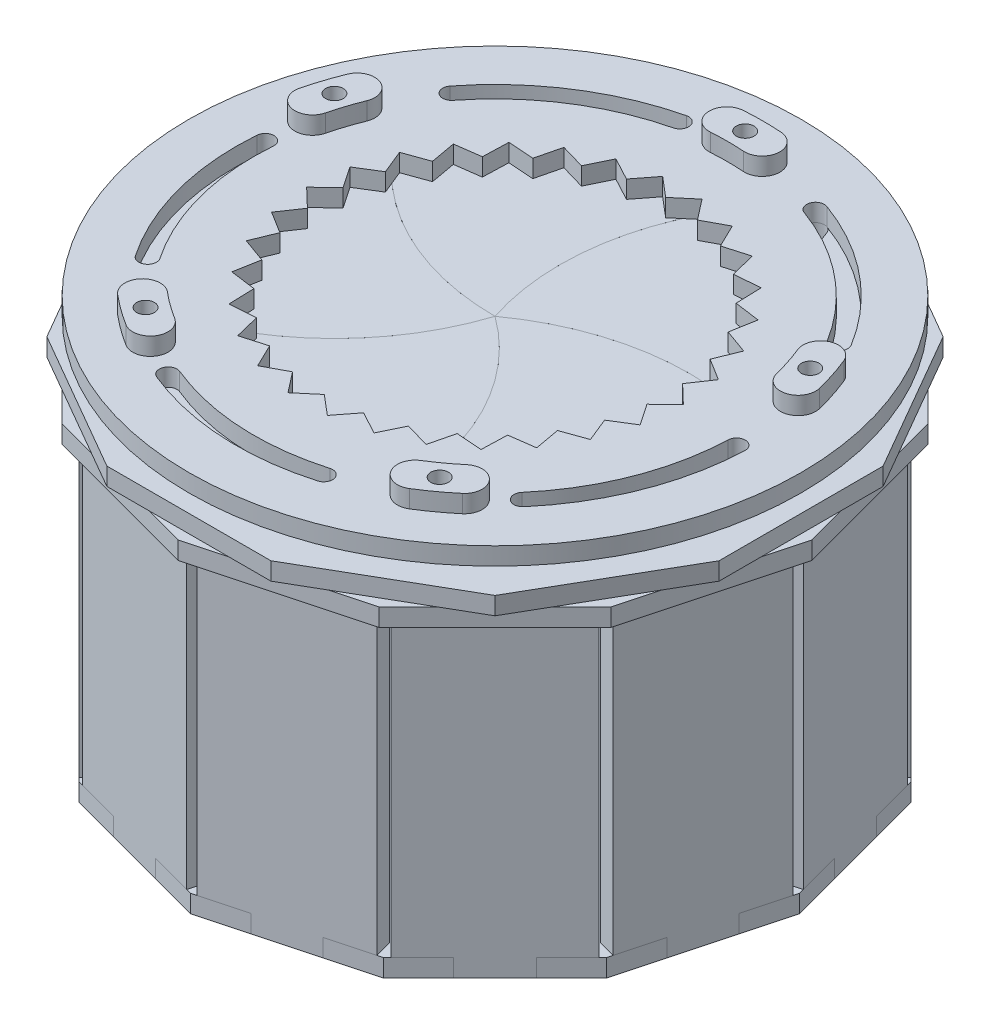
SolidWorks part; units mm, degrees
ref_plane "Front Plane" through (0, 0, 0) normal (0, 0, 1) x (1, 0, 0)
ref_plane "Top Plane" through (0, 0, 0) normal (0, 1, 0) x (1, 0, 0)
ref_plane "Right Plane" through (0, 0, 0) normal (1, 0, 0) x (0, 0, -1)
sketch "Sketch1" plane through (0, 0, 0) normal (0, 1, 0) x (1, 0, 0)
  line L0 (0, 42.5) -> (0, 0) construction
  line L2 (-33.5138, 68.6358) -> (-33.5138, 26.1358) construction
  line L3 (-33.5138, 68.6358) -> (-3.4617, 38.5837) construction
  arc A0 (13.0724, 45.6658) -> (-39.3911, 26.5441) centre (0, 0) ccw
  circle A6 centre (0, 0) radius 42.5 construction
  arc A7 (-39.3911, 26.5441) -> (0, 0) centre (0, 42.5) ccw
  circle A8 centre (0, 42.5) radius 1.5
  arc A9 (39.3911, 26.5441) -> (-39.3911, 26.5441) centre (0, 42.5) ccw construction
  arc A10 (36.8061, 21.25) -> (39.3911, 26.5441) centre (0, 42.5) ccw construction
  arc A11 (0, 0) -> (36.8061, 21.25) centre (0, 42.5) ccw construction
  arc A12 (13.0724, 45.6658) -> (0, 0) centre (40.4199, 13.1332) ccw
  arc A13 (47.4703, 1.6789) -> (0, 0) centre (24.9809, -34.3832) ccw construction
  arc A14 (16.2658, -44.6282) -> (0, 0) centre (-24.9809, -34.3832) ccw construction
  arc A15 (-37.4175, -29.2606) -> (0, 0) centre (-40.4199, 13.1332) ccw construction
  arc A16 (-33.5138, 26.1358) -> (-3.4617, 38.5837) centre (-33.5138, 68.6358) ccw construction
  arc A17 (5.8774, 84.5916) -> (-39.3911, 26.5441) centre (-33.5138, 68.6358) ccw construction
  arc A18 (3.2923, 47.3858) -> (5.8774, 84.5916) centre (-33.5138, 68.6358) ccw construction
  arc A19 (0.9014, 43.6989) -> (3.2923, 47.3858) centre (-33.5138, 68.6358) ccw construction
  arc A20 (0, 42.5) -> (0.9014, 43.6989) centre (-33.5138, 68.6358) ccw construction
  arc A21 (-0.9432, 41.3336) -> (0, 42.5) centre (-33.5138, 68.6358) ccw construction
  arc A22 (-3.4617, 38.5837) -> (-0.9432, 41.3336) centre (-33.5138, 68.6358) ccw construction
  arc A23 (-39.3911, 26.5441) -> (-33.5138, 26.1358) centre (-33.5138, 68.6358) ccw construction
  arc A24 (-3.4617, 38.5837) -> (-33.5138, 26.1358) centre (-33.5138, 68.6358) cw construction
  arc A25 (-33.5138, 24.6358) -> (-2.4011, 37.5231) centre (-33.5138, 68.6358) ccw
  arc A26 (-33.5138, 27.6358) -> (-4.5224, 39.6444) centre (-33.5138, 68.6358) ccw
  arc A27 (-33.5138, 27.6358) -> (-33.5138, 24.6358) centre (-33.5138, 26.1358) ccw
  arc A28 (-2.4011, 37.5231) -> (-4.5224, 39.6444) centre (-3.4617, 38.5837) ccw
  arc A29 (39.3911, 26.5441) -> (13.0724, 45.6658) centre (0, 0) ccw construction
  arc A30 (-39.3911, 26.5441) -> (-37.4175, -29.2606) centre (0, 0) ccw construction
  arc A31 (-37.4175, -29.2606) -> (16.2658, -44.6282) centre (0, 0) ccw construction
  arc A32 (47.4703, 1.6789) -> (39.3911, 26.5441) centre (0, 0) ccw construction
  arc A33 (16.2658, -44.6282) -> (47.4703, 1.6789) centre (0, 0) ccw construction
  point P1 (0, 0)
  point P16 (0, 0)
  point P22 (0, 0)
  point P28 (-17.2497, 29.3709)
  dimension "D1" = 95
  dimension "D3" = 85
  dimension "D5" = 42.5
  dimension "D6" = 5
  dimension "D2" = 3
  dimension "D7" = 1.5
  dimension "D8" = 45
sketch "Sketch3" plane through (0, 0, 0) normal (0, 1, 0) x (1, 0, 0)
  line L0 (8.1113, 49.5904) -> (17.7706, 47.0022)
  line L1 (0, 51.7638) -> (-25.8819, 44.8288) construction
  line L2 (-25.8819, 44.8288) -> (-44.8288, 25.8819) construction
  line L3 (-44.8288, 25.8819) -> (-51.7638, 0) construction
  line L4 (-51.7638, 0) -> (-44.8288, -25.8819) construction
  line L5 (-44.8288, -25.8819) -> (-25.8819, -44.8288) construction
  line L6 (-25.8819, -44.8288) -> (0, -51.7638) construction
  line L7 (0, -51.7638) -> (25.8819, -44.8288) construction
  line L8 (25.8819, -44.8288) -> (44.8288, -25.8819) construction
  line L9 (44.8288, -25.8819) -> (51.7638, 0) construction
  line L10 (51.7638, 0) -> (44.8288, 25.8819) construction
  line L11 (44.8288, 25.8819) -> (25.8819, 44.8288) construction
  line L12 (25.8819, 44.8288) -> (0, 51.7638) construction
  line L13 (8.1113, 49.5904) -> (7.3349, 46.6926)
  line L14 (17.7706, 47.0022) -> (16.9941, 44.1044)
  line L15 (7.3349, 46.6926) -> (16.9941, 44.1044)
  line L16 (12.1645, 45.3985) -> (12.941, 48.2963) construction
  line L17 (26.9172, 46.6219) -> (0, 53.8344)
  line L18 (0, 53.8344) -> (-26.9172, 46.6219)
  line L19 (-26.9172, 46.6219) -> (-46.6219, 26.9172)
  line L20 (-46.6219, 26.9172) -> (-53.8344, 0)
  line L21 (-53.8344, 0) -> (-46.6219, -26.9172)
  line L22 (-46.6219, -26.9172) -> (-26.9172, -46.6219)
  line L23 (-26.9172, -46.6219) -> (0, -53.8344)
  line L24 (0, -53.8344) -> (26.9172, -46.6219)
  line L25 (26.9172, -46.6219) -> (46.6219, -26.9172)
  line L26 (46.6219, -26.9172) -> (53.8344, 0)
  line L27 (53.8344, 0) -> (46.6219, 26.9172)
  line L28 (46.6219, 26.9172) -> (26.9172, 46.6219)
  line L29 (38.8909, 31.8198) -> (36.7696, 29.6985)
  line L30 (31.8198, 38.8909) -> (38.8909, 31.8198)
  line L31 (31.8198, 38.8909) -> (29.6985, 36.7696)
  line L32 (29.6985, 36.7696) -> (36.7696, 29.6985)
  line L33 (33.234, 33.234) -> (35.3553, 35.3553) construction
  line L34 (49.5904, 8.1113) -> (46.6926, 7.3349)
  line L35 (47.0022, 17.7706) -> (49.5904, 8.1113)
  line L36 (47.0022, 17.7706) -> (44.1044, 16.9941)
  line L37 (44.1044, 16.9941) -> (46.6926, 7.3349)
  line L38 (45.3985, 12.1645) -> (48.2963, 12.941) construction
  line L39 (47.0022, -17.7706) -> (44.1044, -16.9941)
  line L40 (49.5904, -8.1113) -> (47.0022, -17.7706)
  line L41 (49.5904, -8.1113) -> (46.6926, -7.3349)
  line L42 (46.6926, -7.3349) -> (44.1044, -16.9941)
  line L43 (45.3985, -12.1645) -> (48.2963, -12.941) construction
  line L44 (31.8198, -38.8909) -> (29.6985, -36.7696)
  line L45 (38.8909, -31.8198) -> (31.8198, -38.8909)
  line L46 (38.8909, -31.8198) -> (36.7696, -29.6985)
  line L47 (36.7696, -29.6985) -> (29.6985, -36.7696)
  line L48 (33.234, -33.234) -> (35.3553, -35.3553) construction
  line L49 (8.1113, -49.5904) -> (7.3349, -46.6926)
  line L50 (17.7706, -47.0022) -> (8.1113, -49.5904)
  line L51 (17.7706, -47.0022) -> (16.9941, -44.1044)
  line L52 (16.9941, -44.1044) -> (7.3349, -46.6926)
  line L53 (12.1645, -45.3985) -> (12.941, -48.2963) construction
  line L54 (-17.7706, -47.0022) -> (-16.9941, -44.1044)
  line L55 (-8.1113, -49.5904) -> (-17.7706, -47.0022)
  line L56 (-8.1113, -49.5904) -> (-7.3349, -46.6926)
  line L57 (-7.3349, -46.6926) -> (-16.9941, -44.1044)
  line L58 (-12.1645, -45.3985) -> (-12.941, -48.2963) construction
  line L59 (-38.8909, -31.8198) -> (-36.7696, -29.6985)
  line L60 (-31.8198, -38.8909) -> (-38.8909, -31.8198)
  line L61 (-31.8198, -38.8909) -> (-29.6985, -36.7696)
  line L62 (-29.6985, -36.7696) -> (-36.7696, -29.6985)
  line L63 (-33.234, -33.234) -> (-35.3553, -35.3553) construction
  line L64 (-49.5904, -8.1113) -> (-46.6926, -7.3349)
  line L65 (-47.0022, -17.7706) -> (-49.5904, -8.1113)
  line L66 (-47.0022, -17.7706) -> (-44.1044, -16.9941)
  line L67 (-44.1044, -16.9941) -> (-46.6926, -7.3349)
  line L68 (-45.3985, -12.1645) -> (-48.2963, -12.941) construction
  line L69 (-47.0022, 17.7706) -> (-44.1044, 16.9941)
  line L70 (-49.5904, 8.1113) -> (-47.0022, 17.7706)
  line L71 (-49.5904, 8.1113) -> (-46.6926, 7.3349)
  line L72 (-46.6926, 7.3349) -> (-44.1044, 16.9941)
  line L73 (-45.3985, 12.1645) -> (-48.2963, 12.941) construction
  line L74 (-31.8198, 38.8909) -> (-29.6985, 36.7696)
  line L75 (-38.8909, 31.8198) -> (-31.8198, 38.8909)
  line L76 (-38.8909, 31.8198) -> (-36.7696, 29.6985)
  line L77 (-36.7696, 29.6985) -> (-29.6985, 36.7696)
  line L78 (-33.234, 33.234) -> (-35.3553, 35.3553) construction
  line L79 (-8.1113, 49.5904) -> (-7.3349, 46.6926)
  line L80 (-17.7706, 47.0022) -> (-8.1113, 49.5904)
  line L81 (-17.7706, 47.0022) -> (-16.9941, 44.1044)
  line L82 (-16.9941, 44.1044) -> (-7.3349, 46.6926)
  line L83 (-12.1645, 45.3985) -> (-12.941, 48.2963) construction
  circle A0 centre (0, 0) radius 50 construction
  circle A2 centre (0, 0) radius 29
  arc A11 (-33.5138, 26.1358) -> (-9.9306, 41.3235) centre (0, 0) cw construction
  arc A20 (-10.281, 42.782) -> (-34.6966, 27.0582) centre (0, 0) ccw
  circle A22 centre (0, 0) radius 42.5 construction
  circle A23 centre (0, 0) radius 42.5 construction
  arc A24 (-9.5801, 39.8651) -> (-32.3309, 25.2133) centre (0, 0) ccw
  arc A25 (-9.5801, 39.8651) -> (-10.281, 42.782) centre (-9.9306, 41.3235) ccw
  arc A26 (-34.6966, 27.0582) -> (-32.3309, 25.2133) centre (-33.5138, 26.1358) ccw
  circle A27 centre (0, 42.5) radius 10 construction
  circle A28 centre (0, 42.5) radius 1.5 construction
  circle A29 centre (0, 42.5) radius 1.5
  circle A30 centre (40.4199, 13.1332) radius 1.5
  arc A31 (14.5003, 39.9499) -> (36.2323, 22.2142) centre (0, 0) cw construction
  arc A32 (37.5111, 22.9982) -> (15.012, 41.3599) centre (0, 0) ccw
  arc A33 (34.9535, 21.4302) -> (13.9885, 38.5399) centre (0, 0) ccw
  arc A34 (34.9535, 21.4302) -> (37.5111, 22.9982) centre (36.2323, 22.2142) ccw
  arc A35 (15.012, 41.3599) -> (13.9885, 38.5399) centre (14.5003, 39.9499) ccw
  circle A36 centre (24.9809, -34.3832) radius 1.5
  arc A37 (42.4754, -1.4454) -> (32.3233, -27.5944) centre (0, 0) cw construction
  arc A38 (33.4642, -28.5683) -> (43.9745, -1.4964) centre (0, 0) ccw
  arc A39 (31.1825, -26.6205) -> (40.9763, -1.3944) centre (0, 0) ccw
  arc A40 (31.1825, -26.6205) -> (33.4642, -28.5683) centre (32.3233, -27.5944) ccw
  arc A41 (43.9745, -1.4964) -> (40.9763, -1.3944) centre (42.4754, -1.4454) ccw
  circle A42 centre (-24.9809, -34.3832) radius 1.5
  arc A43 (11.751, -40.8432) -> (-16.2554, -39.2685) centre (0, 0) cw construction
  arc A44 (-16.8291, -40.6544) -> (12.1657, -42.2847) centre (0, 0) ccw
  arc A45 (-15.6817, -37.8825) -> (11.3362, -39.4016) centre (0, 0) ccw
  arc A46 (-15.6817, -37.8825) -> (-16.8291, -40.6544) centre (-16.2554, -39.2685) ccw
  arc A47 (12.1657, -42.2847) -> (11.3362, -39.4016) centre (11.751, -40.8432) ccw
  circle A48 centre (-40.4199, 13.1332) radius 1.5
  arc A49 (-35.2129, -23.7971) -> (-42.3697, 3.3252) centre (0, 0) cw construction
  arc A50 (-43.8651, 3.4425) -> (-36.4557, -24.637) centre (0, 0) ccw
  arc A51 (-40.8743, 3.2078) -> (-33.9701, -22.9572) centre (0, 0) ccw
  arc A52 (-40.8743, 3.2078) -> (-43.8651, 3.4425) centre (-42.3697, 3.3252) ccw
  arc A53 (-36.4557, -24.637) -> (-33.9701, -22.9572) centre (-35.2129, -23.7971) ccw
  circle A54 centre (0, 0) radius 52 construction
  point P1 (-23.0113, 35.7314)
  point P102 (0, 0)
  point P106 (-9.9306, 41.3235)
  point P121 (26.8717, 32.9266)
  point P132 (39.6189, -15.3816)
  point P141 (-2.3859, -42.433)
  point P150 (-41.0934, -10.8434)
  point P159 (0, 0)
  dimension "D1" = 100
  dimension "D6" = 58
  dimension "D7" = 1.5
  dimension "D8" = 20
  dimension "D2" = 3
  dimension "D3" = 10
  dimension "D4" = 2
  dimension "D5" = 12
  dimension "D9" = 5
sketch "Sketch4" plane through (0, 0, 0) normal (0, 1, 0) x (1, 0, 0)
  arc A0 (6.0367, 38.1141) -> (5.8444, 47.1391) centre (0, 42.5) ccw
  circle A1 centre (0, 42.5) radius 1.5
  circle A2 centre (0, 42.5) radius 1.5
  arc A3 (-5.8444, 47.1391) -> (-6.0765, 38.1694) centre (0, 42.5) ccw construction
  arc A4 (5.8444, 47.1391) -> (-5.8444, 47.1391) centre (0, 42.5) ccw construction
  arc A5 (13.0724, 45.6658) -> (-39.3911, 26.5441) centre (0, 0) ccw
  arc A6 (-39.3911, 26.5441) -> (0, 0) centre (0, 42.5) ccw
  arc A7 (13.0724, 45.6658) -> (0, 0) centre (40.4199, 13.1332) ccw
  arc A8 (5.8444, 47.1391) -> (-39.3911, 26.5441) centre (0, 0) ccw
  arc A9 (-39.3911, 26.5441) -> (0, 0) centre (0, 42.5) ccw
  arc A10 (6.0367, 38.1141) -> (0, 0) centre (40.4199, 13.1332) ccw
  arc A11 (-6.0765, 38.1694) -> (-3.8701, 36.1203) centre (0, 42.5) ccw construction
  arc A12 (-2.4011, 37.5231) -> (-4.5224, 39.6444) centre (-3.4617, 38.5837) ccw
  arc A13 (-33.5138, 24.6358) -> (-2.4011, 37.5231) centre (-33.5138, 68.6358) ccw
  arc A14 (-33.5138, 27.6358) -> (-33.5138, 24.6358) centre (-33.5138, 26.1358) ccw
  arc A15 (-33.5138, 27.6358) -> (-4.5224, 39.6444) centre (-33.5138, 68.6358) ccw
  arc A16 (-2.4011, 37.5231) -> (-4.5224, 39.6444) centre (-3.4617, 38.5837) ccw
  arc A17 (-33.5138, 24.6358) -> (-2.4011, 37.5231) centre (-33.5138, 68.6358) ccw
  arc A18 (-33.5138, 27.6358) -> (-33.5138, 24.6358) centre (-33.5138, 26.1358) ccw
  arc A19 (-33.5138, 27.6358) -> (-4.5224, 39.6444) centre (-33.5138, 68.6358) ccw
  arc A20 (-3.8701, 36.1203) -> (6.0367, 38.1141) centre (0, 42.5) ccw construction
  arc A21 (13.0724, 45.6658) -> (6.0367, 38.1141) centre (40.4199, 13.1332) ccw construction
  arc A22 (13.0724, 45.6658) -> (5.8444, 47.1391) centre (0, 0) ccw construction
  arc A23 (5.738, 46.9507) -> (-39.1657, 26.5206) centre (0, 0) ccw construction
  arc A24 (-39.1657, 26.5206) -> (-0.2746, 0.2009) centre (0, 42.5) ccw construction
  arc A25 (5.8749, 38.2317) -> (-0.2746, 0.2009) centre (40.4199, 13.1332) ccw construction
  arc A26 (5.8749, 38.2317) -> (5.738, 46.9507) centre (0, 42.5) ccw construction
  dimension "D1" = 0
  dimension "D2" = 0
  dimension "D3" = 0
  dimension "D4" = 0.2
extrude "Boss-Extrude1" add sketch "Sketch4" against normal blind 3
sketch "Sketch5" plane through (0, 0, 0) normal (0, 1, 0) x (1, 0, 0)
  line L0 (0, 0) -> (0, 32) construction
  line L1 (0, 0) -> (3.3449, 31.8247) construction
  line L2 (0, 0) -> (-3.3449, 31.8247) construction
  line L3 (-3.3449, 31.8247) -> (0, 29)
  line L4 (0, 29) -> (3.3449, 31.8247)
  line L6 (3.3449, 31.8247) -> (6.0294, 28.3663)
  line L7 (6.0294, 28.3663) -> (9.8885, 30.4338)
  line L8 (9.8885, 30.4338) -> (11.7954, 26.4928)
  line L9 (11.7954, 26.4928) -> (16, 27.7128)
  line L10 (16, 27.7128) -> (17.0458, 23.4615)
  line L11 (17.0458, 23.4615) -> (21.4122, 23.7806)
  line L12 (21.4122, 23.7806) -> (21.5512, 19.4048)
  line L13 (21.5512, 19.4048) -> (25.8885, 18.8091)
  line L14 (25.8885, 18.8091) -> (25.1147, 14.5)
  line L15 (25.1147, 14.5) -> (29.2335, 13.0156)
  line L16 (29.2335, 13.0156) -> (27.5806, 8.9615)
  line L17 (27.5806, 8.9615) -> (31.3007, 6.6532)
  line L18 (31.3007, 6.6532) -> (28.8411, 3.0313)
  line L19 (28.8411, 3.0313) -> (32, 0)
  line L20 (32, 0) -> (28.8411, -3.0313)
  line L21 (28.8411, -3.0313) -> (31.3007, -6.6532)
  line L22 (31.3007, -6.6532) -> (27.5806, -8.9615)
  line L23 (27.5806, -8.9615) -> (29.2335, -13.0156)
  line L24 (29.2335, -13.0156) -> (25.1147, -14.5)
  line L25 (25.1147, -14.5) -> (25.8885, -18.8091)
  line L26 (25.8885, -18.8091) -> (21.5512, -19.4048)
  line L27 (21.5512, -19.4048) -> (21.4122, -23.7806)
  line L28 (21.4122, -23.7806) -> (17.0458, -23.4615)
  line L29 (17.0458, -23.4615) -> (16, -27.7128)
  line L30 (16, -27.7128) -> (11.7954, -26.4928)
  line L31 (11.7954, -26.4928) -> (9.8885, -30.4338)
  line L32 (9.8885, -30.4338) -> (6.0294, -28.3663)
  line L33 (6.0294, -28.3663) -> (3.3449, -31.8247)
  line L34 (3.3449, -31.8247) -> (0, -29)
  line L35 (0, -29) -> (-3.3449, -31.8247)
  line L36 (-3.3449, -31.8247) -> (-6.0294, -28.3663)
  line L37 (-6.0294, -28.3663) -> (-9.8885, -30.4338)
  line L38 (-9.8885, -30.4338) -> (-11.7954, -26.4928)
  line L39 (-11.7954, -26.4928) -> (-16, -27.7128)
  line L40 (-16, -27.7128) -> (-17.0458, -23.4615)
  line L41 (-17.0458, -23.4615) -> (-21.4122, -23.7806)
  line L42 (-21.4122, -23.7806) -> (-21.5512, -19.4048)
  line L43 (-21.5512, -19.4048) -> (-25.8885, -18.8091)
  line L44 (-25.8885, -18.8091) -> (-25.1147, -14.5)
  line L45 (-25.1147, -14.5) -> (-29.2335, -13.0156)
  line L46 (-29.2335, -13.0156) -> (-27.5806, -8.9615)
  line L47 (-27.5806, -8.9615) -> (-31.3007, -6.6532)
  line L48 (-31.3007, -6.6532) -> (-28.8411, -3.0313)
  line L49 (-28.8411, -3.0313) -> (-32, 0)
  line L50 (-32, 0) -> (-28.8411, 3.0313)
  line L51 (-28.8411, 3.0313) -> (-31.3007, 6.6532)
  line L52 (-31.3007, 6.6532) -> (-27.5806, 8.9615)
  line L53 (-27.5806, 8.9615) -> (-29.2335, 13.0156)
  line L54 (-29.2335, 13.0156) -> (-25.1147, 14.5)
  line L55 (-25.1147, 14.5) -> (-25.8885, 18.8091)
  line L56 (-25.8885, 18.8091) -> (-21.5512, 19.4048)
  line L57 (-21.5512, 19.4048) -> (-21.4122, 23.7806)
  line L58 (-21.4122, 23.7806) -> (-17.0458, 23.4615)
  line L59 (-17.0458, 23.4615) -> (-16, 27.7128)
  line L60 (-16, 27.7128) -> (-11.7954, 26.4928)
  line L61 (-11.7954, 26.4928) -> (-9.8885, 30.4338)
  line L62 (-9.8885, 30.4338) -> (-6.0294, 28.3663)
  line L63 (-6.0294, 28.3663) -> (-3.3449, 31.8247)
  circle A2 centre (0, 0) radius 32 construction
  circle A3 centre (0, 0) radius 52 construction
  circle A4 centre (0, 0) radius 52
  circle A6 centre (24.9809, -34.3832) radius 1.35
  circle A7 centre (0, 0) radius 29
  circle A8 centre (0, 0) radius 29 construction
  circle A9 centre (0, 42.5) radius 1.5
  circle A10 centre (0, 42.5) radius 1.5 construction
  circle A11 centre (24.9809, -34.3832) radius 1.5
  circle A12 centre (24.9809, -34.3832) radius 1.5 construction
  circle A13 centre (40.4199, 13.1332) radius 1.5
  arc A14 (-9.5801, 39.8651) -> (-32.3309, 25.2133) centre (0, 0) ccw
  arc A15 (-9.5801, 39.8651) -> (-10.281, 42.782) centre (-9.9306, 41.3235) ccw
  arc A16 (-10.281, 42.782) -> (-34.6966, 27.0582) centre (0, 0) ccw
  arc A17 (-34.6966, 27.0582) -> (-32.3309, 25.2133) centre (-33.5138, 26.1358) ccw
  arc A18 (-9.5801, 39.8651) -> (-32.3309, 25.2133) centre (0, 0) ccw
  arc A19 (-9.5801, 39.8651) -> (-10.281, 42.782) centre (-9.9306, 41.3235) ccw
  arc A20 (-10.281, 42.782) -> (-34.6966, 27.0582) centre (0, 0) ccw
  arc A21 (-34.6966, 27.0582) -> (-32.3309, 25.2133) centre (-33.5138, 26.1358) ccw
  arc A22 (33.4642, -28.5683) -> (43.9745, -1.4964) centre (0, 0) ccw
  arc A23 (43.9745, -1.4964) -> (40.9763, -1.3944) centre (42.4754, -1.4454) ccw
  arc A24 (31.1825, -26.6205) -> (40.9763, -1.3944) centre (0, 0) ccw
  arc A25 (31.1825, -26.6205) -> (33.4642, -28.5683) centre (32.3233, -27.5944) ccw
  arc A26 (33.4642, -28.5683) -> (43.9745, -1.4964) centre (0, 0) ccw
  arc A27 (43.9745, -1.4964) -> (40.9763, -1.3944) centre (42.4754, -1.4454) ccw
  arc A28 (31.1825, -26.6205) -> (40.9763, -1.3944) centre (0, 0) ccw
  arc A29 (31.1825, -26.6205) -> (33.4642, -28.5683) centre (32.3233, -27.5944) ccw
  circle A30 centre (40.4199, 13.1332) radius 1.5 construction
  circle A31 centre (-40.4199, 13.1332) radius 1.5
  arc A32 (15.012, 41.3599) -> (13.9885, 38.5399) centre (14.5003, 39.9499) ccw
  arc A33 (37.5111, 22.9982) -> (15.012, 41.3599) centre (0, 0) ccw
  arc A34 (34.9535, 21.4302) -> (37.5111, 22.9982) centre (36.2323, 22.2142) ccw
  arc A35 (34.9535, 21.4302) -> (13.9885, 38.5399) centre (0, 0) ccw
  arc A36 (15.012, 41.3599) -> (13.9885, 38.5399) centre (14.5003, 39.9499) ccw
  arc A37 (37.5111, 22.9982) -> (15.012, 41.3599) centre (0, 0) ccw
  arc A38 (34.9535, 21.4302) -> (37.5111, 22.9982) centre (36.2323, 22.2142) ccw
  arc A39 (34.9535, 21.4302) -> (13.9885, 38.5399) centre (0, 0) ccw
  circle A40 centre (-40.4199, 13.1332) radius 1.5 construction
  circle A41 centre (-24.9809, -34.3832) radius 1.5
  arc A42 (-43.8651, 3.4425) -> (-36.4557, -24.637) centre (0, 0) ccw
  arc A43 (-36.4557, -24.637) -> (-33.9701, -22.9572) centre (-35.2129, -23.7971) ccw
  arc A44 (-40.8743, 3.2078) -> (-33.9701, -22.9572) centre (0, 0) ccw
  arc A45 (-40.8743, 3.2078) -> (-43.8651, 3.4425) centre (-42.3697, 3.3252) ccw
  arc A46 (-43.8651, 3.4425) -> (-36.4557, -24.637) centre (0, 0) ccw
  arc A47 (-36.4557, -24.637) -> (-33.9701, -22.9572) centre (-35.2129, -23.7971) ccw
  arc A48 (-40.8743, 3.2078) -> (-33.9701, -22.9572) centre (0, 0) ccw
  arc A49 (-40.8743, 3.2078) -> (-43.8651, 3.4425) centre (-42.3697, 3.3252) ccw
  circle A50 centre (-24.9809, -34.3832) radius 1.5 construction
  circle A51 centre (40.4199, 13.1332) radius 1.35
  arc A52 (-15.6817, -37.8825) -> (11.3362, -39.4016) centre (0, 0) ccw
  arc A53 (12.1657, -42.2847) -> (11.3362, -39.4016) centre (11.751, -40.8432) ccw
  arc A54 (-16.8291, -40.6544) -> (12.1657, -42.2847) centre (0, 0) ccw
  arc A55 (-15.6817, -37.8825) -> (-16.8291, -40.6544) centre (-16.2554, -39.2685) ccw
  arc A56 (-15.6817, -37.8825) -> (11.3362, -39.4016) centre (0, 0) ccw
  arc A57 (12.1657, -42.2847) -> (11.3362, -39.4016) centre (11.751, -40.8432) ccw
  arc A58 (-16.8291, -40.6544) -> (12.1657, -42.2847) centre (0, 0) ccw
  arc A59 (-15.6817, -37.8825) -> (-16.8291, -40.6544) centre (-16.2554, -39.2685) ccw
  circle A60 centre (-24.9809, -34.3832) radius 1.35
  circle A61 centre (-40.4199, 13.1332) radius 1.35
  circle A62 centre (0, 42.5) radius 1.35
  point P166 (0, 0)
  dimension "D4" = 3
  dimension "D3" = 2.7
  dimension "D5" = 6
  dimension "D6" = 6
  dimension "D2" = 0
  dimension "D7" = 30
  dimension "D15" = 0
  dimension "D16" = 0
  dimension "D17" = 0
  dimension "D18" = 0
  dimension "D19" = 0
  dimension "D20" = 0
  dimension "D21" = 0
  dimension "D22" = 0
  dimension "D23" = 0
  dimension "D24" = 0
extrude "Boss-Extrude2" add sketch "Sketch5" along normal blind 3 separate body
sketch "Sketch8" plane through (0, 0, 0) normal (0, 1, 0) x (1, 0, 0)
  line L0 (26.9172, 46.6219) -> (0, 53.8344) construction
  line L1 (13.9334, 52) -> (-13.9334, 52)
  line L2 (-13.9334, 52) -> (-38.0666, 38.0666)
  line L3 (-38.0666, 38.0666) -> (-52, 13.9334)
  line L4 (-52, 13.9334) -> (-52, -13.9334)
  line L5 (-52, -13.9334) -> (-38.0666, -38.0666)
  line L6 (-38.0666, -38.0666) -> (-13.9334, -52)
  line L7 (-13.9334, -52) -> (13.9334, -52)
  line L8 (13.9334, -52) -> (38.0666, -38.0666)
  line L9 (38.0666, -38.0666) -> (52, -13.9334)
  line L10 (52, -13.9334) -> (52, 13.9334)
  line L11 (52, 13.9334) -> (38.0666, 38.0666)
  line L12 (38.0666, 38.0666) -> (13.9334, 52)
  circle A0 centre (14.5003, 39.9499) radius 1.35
  circle A1 centre (42.4754, -1.4454) radius 1.35
  circle A2 centre (11.751, -40.8432) radius 1.35
  circle A3 centre (-35.2129, -23.7971) radius 1.35
  circle A4 centre (-33.5138, 26.1358) radius 1.35
  circle A5 centre (0, 0) radius 52 construction
  circle A8 centre (0, 0) radius 37
  circle A9 centre (0, 0) radius 37
  point P3 (0, 52)
  point P14 (0, 0)
  dimension "D1" = 2.7
  dimension "D3" = 8
  dimension "D2" = 5
extrude "Boss-Extrude5" add sketch "Sketch8" against normal blind 3 from surface separate body starting at face at (-17.9786, -3, -31.1305)
sketch "Sketch6" plane through (0, 0, 0) normal (0, 1, 0) x (1, 0, 0)
  line L4 (17.7706, 47.0022) -> (8.1113, 49.5904)
  line L5 (16.9941, 44.1044) -> (17.7706, 47.0022)
  line L6 (7.3349, 46.6926) -> (16.9941, 44.1044)
  line L7 (8.1113, 49.5904) -> (7.3349, 46.6926)
  line L8 (17.7706, 47.0022) -> (8.1113, 49.5904)
  line L9 (16.9941, 44.1044) -> (17.7706, 47.0022)
  line L10 (7.3349, 46.6926) -> (16.9941, 44.1044)
  line L11 (8.1113, 49.5904) -> (7.3349, 46.6926)
  line L12 (46.6926, 7.3349) -> (49.5904, 8.1113)
  line L13 (44.1044, 16.9941) -> (46.6926, 7.3349)
  line L14 (47.0022, 17.7706) -> (44.1044, 16.9941)
  line L15 (49.5904, 8.1113) -> (47.0022, 17.7706)
  line L16 (46.6926, 7.3349) -> (49.5904, 8.1113)
  line L17 (44.1044, 16.9941) -> (46.6926, 7.3349)
  line L18 (47.0022, 17.7706) -> (44.1044, 16.9941)
  line L19 (49.5904, 8.1113) -> (47.0022, 17.7706)
  line L20 (36.7696, 29.6985) -> (38.8909, 31.8198)
  line L21 (29.6985, 36.7696) -> (36.7696, 29.6985)
  line L22 (31.8198, 38.8909) -> (29.6985, 36.7696)
  line L23 (38.8909, 31.8198) -> (31.8198, 38.8909)
  line L24 (36.7696, 29.6985) -> (38.8909, 31.8198)
  line L25 (29.6985, 36.7696) -> (36.7696, 29.6985)
  line L26 (31.8198, 38.8909) -> (29.6985, 36.7696)
  line L27 (38.8909, 31.8198) -> (31.8198, 38.8909)
  line L28 (29.6985, -36.7696) -> (31.8198, -38.8909)
  line L29 (36.7696, -29.6985) -> (29.6985, -36.7696)
  line L30 (38.8909, -31.8198) -> (36.7696, -29.6985)
  line L31 (31.8198, -38.8909) -> (38.8909, -31.8198)
  line L32 (29.6985, -36.7696) -> (31.8198, -38.8909)
  line L33 (36.7696, -29.6985) -> (29.6985, -36.7696)
  line L34 (38.8909, -31.8198) -> (36.7696, -29.6985)
  line L35 (31.8198, -38.8909) -> (38.8909, -31.8198)
  line L36 (46.6219, -26.9172) -> (53.8344, 0)
  line L37 (53.8344, 0) -> (46.6219, 26.9172)
  line L38 (46.6219, 26.9172) -> (26.9172, 46.6219)
  line L39 (26.9172, 46.6219) -> (0, 53.8344)
  line L40 (0, 53.8344) -> (-26.9172, 46.6219)
  line L41 (-26.9172, 46.6219) -> (-46.6219, 26.9172)
  line L42 (-46.6219, 26.9172) -> (-53.8344, 0)
  line L43 (-53.8344, 0) -> (-46.6219, -26.9172)
  line L44 (-46.6219, -26.9172) -> (-26.9172, -46.6219)
  line L45 (-26.9172, -46.6219) -> (0, -53.8344)
  line L46 (0, -53.8344) -> (26.9172, -46.6219)
  line L47 (26.9172, -46.6219) -> (46.6219, -26.9172)
  line L48 (46.6219, -26.9172) -> (53.8344, 0)
  line L49 (53.8344, 0) -> (46.6219, 26.9172)
  line L50 (46.6219, 26.9172) -> (26.9172, 46.6219)
  line L51 (26.9172, 46.6219) -> (0, 53.8344)
  line L52 (0, 53.8344) -> (-26.9172, 46.6219)
  line L53 (-26.9172, 46.6219) -> (-46.6219, 26.9172)
  line L54 (-46.6219, 26.9172) -> (-53.8344, 0)
  line L55 (-53.8344, 0) -> (-46.6219, -26.9172)
  line L56 (-46.6219, -26.9172) -> (-26.9172, -46.6219)
  line L57 (-26.9172, -46.6219) -> (0, -53.8344)
  line L58 (0, -53.8344) -> (26.9172, -46.6219)
  line L59 (26.9172, -46.6219) -> (46.6219, -26.9172)
  line L60 (44.1044, -16.9941) -> (47.0022, -17.7706)
  line L61 (46.6926, -7.3349) -> (44.1044, -16.9941)
  line L62 (49.5904, -8.1113) -> (46.6926, -7.3349)
  line L63 (47.0022, -17.7706) -> (49.5904, -8.1113)
  line L64 (44.1044, -16.9941) -> (47.0022, -17.7706)
  line L65 (46.6926, -7.3349) -> (44.1044, -16.9941)
  line L66 (49.5904, -8.1113) -> (46.6926, -7.3349)
  line L67 (47.0022, -17.7706) -> (49.5904, -8.1113)
  line L68 (-36.7696, -29.6985) -> (-38.8909, -31.8198)
  line L69 (-29.6985, -36.7696) -> (-36.7696, -29.6985)
  line L70 (-31.8198, -38.8909) -> (-29.6985, -36.7696)
  line L71 (-38.8909, -31.8198) -> (-31.8198, -38.8909)
  line L72 (-36.7696, -29.6985) -> (-38.8909, -31.8198)
  line L73 (-29.6985, -36.7696) -> (-36.7696, -29.6985)
  line L74 (-31.8198, -38.8909) -> (-29.6985, -36.7696)
  line L75 (-38.8909, -31.8198) -> (-31.8198, -38.8909)
  line L76 (-16.9941, -44.1044) -> (-17.7706, -47.0022)
  line L77 (-7.3349, -46.6926) -> (-16.9941, -44.1044)
  line L78 (-8.1113, -49.5904) -> (-7.3349, -46.6926)
  line L79 (-17.7706, -47.0022) -> (-8.1113, -49.5904)
  line L80 (-16.9941, -44.1044) -> (-17.7706, -47.0022)
  line L81 (-7.3349, -46.6926) -> (-16.9941, -44.1044)
  line L82 (-8.1113, -49.5904) -> (-7.3349, -46.6926)
  line L83 (-17.7706, -47.0022) -> (-8.1113, -49.5904)
  line L84 (16.9941, -44.1044) -> (7.3349, -46.6926)
  line L85 (7.3349, -46.6926) -> (8.1113, -49.5904)
  line L86 (8.1113, -49.5904) -> (17.7706, -47.0022)
  line L87 (17.7706, -47.0022) -> (16.9941, -44.1044)
  line L88 (16.9941, -44.1044) -> (7.3349, -46.6926)
  line L89 (7.3349, -46.6926) -> (8.1113, -49.5904)
  line L90 (8.1113, -49.5904) -> (17.7706, -47.0022)
  line L91 (17.7706, -47.0022) -> (16.9941, -44.1044)
  line L92 (-29.6985, 36.7696) -> (-31.8198, 38.8909)
  line L93 (-36.7696, 29.6985) -> (-29.6985, 36.7696)
  line L94 (-38.8909, 31.8198) -> (-36.7696, 29.6985)
  line L95 (-31.8198, 38.8909) -> (-38.8909, 31.8198)
  line L96 (-29.6985, 36.7696) -> (-31.8198, 38.8909)
  line L97 (-36.7696, 29.6985) -> (-29.6985, 36.7696)
  line L98 (-38.8909, 31.8198) -> (-36.7696, 29.6985)
  line L99 (-31.8198, 38.8909) -> (-38.8909, 31.8198)
  line L100 (-44.1044, 16.9941) -> (-47.0022, 17.7706)
  line L101 (-46.6926, 7.3349) -> (-44.1044, 16.9941)
  line L102 (-49.5904, 8.1113) -> (-46.6926, 7.3349)
  line L103 (-47.0022, 17.7706) -> (-49.5904, 8.1113)
  line L104 (-44.1044, 16.9941) -> (-47.0022, 17.7706)
  line L105 (-46.6926, 7.3349) -> (-44.1044, 16.9941)
  line L106 (-49.5904, 8.1113) -> (-46.6926, 7.3349)
  line L107 (-47.0022, 17.7706) -> (-49.5904, 8.1113)
  line L108 (-46.6926, -7.3349) -> (-49.5904, -8.1113)
  line L109 (-49.5904, -8.1113) -> (-47.0022, -17.7706)
  line L110 (-47.0022, -17.7706) -> (-44.1044, -16.9941)
  line L111 (-44.1044, -16.9941) -> (-46.6926, -7.3349)
  line L112 (-46.6926, -7.3349) -> (-49.5904, -8.1113)
  line L113 (-49.5904, -8.1113) -> (-47.0022, -17.7706)
  line L114 (-47.0022, -17.7706) -> (-44.1044, -16.9941)
  line L115 (-44.1044, -16.9941) -> (-46.6926, -7.3349)
  line L116 (-7.3349, 46.6926) -> (-8.1113, 49.5904)
  line L117 (-16.9941, 44.1044) -> (-7.3349, 46.6926)
  line L118 (-17.7706, 47.0022) -> (-16.9941, 44.1044)
  line L119 (-8.1113, 49.5904) -> (-17.7706, 47.0022)
  line L120 (-7.3349, 46.6926) -> (-8.1113, 49.5904)
  line L121 (-16.9941, 44.1044) -> (-7.3349, 46.6926)
  line L122 (-17.7706, 47.0022) -> (-16.9941, 44.1044)
  line L123 (-8.1113, 49.5904) -> (-17.7706, 47.0022)
  circle A0 centre (0, 0) radius 37
  circle A1 centre (0, 0) radius 29
  circle A2 centre (0, 0) radius 29 construction
  circle A5 centre (-33.5138, 26.1358) radius 1.35
  circle A45 centre (14.5003, 39.9499) radius 1.35
  circle A54 centre (42.4754, -1.4454) radius 1.35
  circle A55 centre (11.751, -40.8432) radius 1.35
  circle A56 centre (-35.2129, -23.7971) radius 1.35
  point P68 (0, 0)
  point P70 (44.4754, 0.5535)
  point P71 (0, 0)
  point P87 (0, 0)
  dimension "D16" = 2.7
  dimension "D1" = 0
  dimension "D2" = 0
  dimension "D3" = 0
  dimension "D4" = 0
  dimension "D5" = 0
  dimension "D6" = 0
  dimension "D7" = 0
  dimension "D8" = 0
  dimension "D9" = 0
  dimension "D10" = 0
  dimension "D11" = 0
  dimension "D12" = 0
  dimension "D13" = 0
  dimension "D14" = 0
  dimension "D15" = 8
  dimension "D18" = 5
extrude "Boss-Extrude6" add sketch "Sketch6" against normal blind 3 from surface separate body starting at face at (0, -6, 37)
sketch "Sketch7" plane through (0, 0, 0) normal (0, 1, 0) x (1, 0, 0)
  circle A16 centre (0, 42.5) radius 1.5 construction
  arc A20 (-3, 42.394) -> (3, 42.394) centre (0, 0) cw construction
  arc A22 (3.2118, 45.3865) -> (-3.2118, 45.3865) centre (0, 0) ccw
  arc A23 (2.7882, 39.4015) -> (-2.7882, 39.4015) centre (0, 0) ccw
  arc A24 (2.7882, 39.4015) -> (3.2118, 45.3865) centre (3, 42.394) ccw
  arc A25 (-3.2118, 45.3865) -> (-2.7882, 39.4015) centre (-3, 42.394) ccw
  circle A26 centre (0, 42.5) radius 1.5
  point P5 (0, 42.5)
  dimension "D1" = 3
  dimension "D2" = 6
  dimension "D3" = 3
extrude "Boss-Extrude4" add sketch "Sketch7" along normal blind 3 from surface separate body starting at face at (-40.4199, 3, -11.7832)
ref_plane "Plane2" through (-12.1645, 0, -45.3985) normal (-0.2588, 0, -0.9659) x (-0.9659, 0, 0.2588)
sketch "Sketch9" plane through (-12.1645, 0, -45.3985) normal (-0.2588, 0, -0.9659) x (-0.9659, 0, 0.2588)
  line L0 (-13.9334, -9) -> (13.9334, -9) construction
  line L1 (12.5, -59) -> (-12.5, -59)
  line L2 (12.5, -59) -> (12.5, -9)
  line L3 (12.5, -9) -> (-12.5, -9)
  line L4 (-12.5, -59) -> (-12.5, -9)
  line L5 (12.5, -59) -> (-12.5, -9) construction
  line L6 (12.5, -9) -> (-12.5, -59) construction
  line L8 (-5, -59) -> (5, -59)
  line L9 (-5, -59) -> (-5, -62)
  line L10 (-5, -62) -> (5, -62)
  line L11 (5, -6) -> (-5, -6)
  line L12 (-5, -6) -> (-5, -9)
  line L13 (-5, -9) -> (5, -9)
  line L14 (5, -9) -> (5, -6)
  line L15 (5, -6) -> (-5, -6)
  line L16 (-5, -6) -> (-5, -9)
  line L17 (-5, -9) -> (5, -9)
  line L18 (5, -9) -> (5, -6)
  line L19 (5, -59) -> (5, -62)
  point P0 (0, -34)
  point P9 (0, -9)
  point P11 (0, -62)
  dimension "D1" = 50
  dimension "D3" = 25
  dimension "D2" = 0
extrude "Boss-Extrude7" add sketch "Sketch9" along normal blind 3 separate body contours L4 L1 L2 L3 | L3 L18 L15 L16 | L19 L1 L9 L10 region at (-12.1645, -34, -45.3985) region at (-12.1645, -60.5, -45.3985) region at (-12.1645, -7.5, -45.3985)
ref_axis "Axis1" through (0, 9.4, 0) along (0, -1, 0)
pattern_circular "CirPattern1" count 12 over 360 about axis through (0, 9.4, 0) along (0, -1, 0) of bodies 111
sketch "Sketch10" plane through (0, 0, 0) normal (0, 1, 0) x (1, 0, 0)
  line L0 (-17.7706, -47.0022) -> (-8.1113, -49.5904) construction
  line L1 (0, -51.7638) -> (25.8819, -44.8288)
  line L2 (25.8819, -44.8288) -> (44.8288, -25.8819)
  line L3 (44.8288, -25.8819) -> (51.7638, 0)
  line L4 (51.7638, 0) -> (44.8288, 25.8819)
  line L5 (44.8288, 25.8819) -> (25.8819, 44.8288)
  line L6 (25.8819, 44.8288) -> (0, 51.7638)
  line L7 (0, 51.7638) -> (-25.8819, 44.8288)
  line L8 (-25.8819, 44.8288) -> (-44.8288, 25.8819)
  line L9 (-44.8288, 25.8819) -> (-51.7638, 0)
  line L10 (-51.7638, 0) -> (-44.8288, -25.8819)
  line L11 (-44.8288, -25.8819) -> (-25.8819, -44.8288)
  line L12 (-25.8819, -44.8288) -> (0, -51.7638)
  line L13 (-36.7696, -29.6985) -> (-29.6985, -36.7696) construction
  line L14 (-29.6985, -36.7696) -> (-31.8198, -38.8909) construction
  line L15 (-31.8198, -38.8909) -> (-38.8909, -31.8198) construction
  line L16 (-38.8909, -31.8198) -> (-36.7696, -29.6985) construction
  line L17 (-16.9941, -44.1044) -> (-7.3349, -46.6926) construction
  line L18 (-7.3349, -46.6926) -> (-8.1113, -49.5904) construction
  line L19 (-8.1113, -49.5904) -> (-17.7706, -47.0022) construction
  line L20 (-17.7706, -47.0022) -> (-16.9941, -44.1044) construction
  line L21 (7.3349, -46.6926) -> (16.9941, -44.1044) construction
  line L22 (16.9941, -44.1044) -> (17.7706, -47.0022) construction
  line L23 (17.7706, -47.0022) -> (8.1113, -49.5904) construction
  line L24 (8.1113, -49.5904) -> (7.3349, -46.6926) construction
  line L25 (29.6985, -36.7696) -> (36.7696, -29.6985) construction
  line L26 (36.7696, -29.6985) -> (38.8909, -31.8198) construction
  line L27 (38.8909, -31.8198) -> (31.8198, -38.8909) construction
  line L28 (31.8198, -38.8909) -> (29.6985, -36.7696) construction
  line L29 (44.1044, -16.9941) -> (46.6926, -7.3349) construction
  line L30 (46.6926, -7.3349) -> (49.5904, -8.1113) construction
  line L31 (49.5904, -8.1113) -> (47.0022, -17.7706) construction
  line L32 (47.0022, -17.7706) -> (44.1044, -16.9941) construction
  line L33 (46.6926, 7.3349) -> (44.1044, 16.9941) construction
  line L34 (44.1044, 16.9941) -> (47.0022, 17.7706) construction
  line L35 (47.0022, 17.7706) -> (49.5904, 8.1113) construction
  line L36 (49.5904, 8.1113) -> (46.6926, 7.3349) construction
  line L37 (36.7696, 29.6985) -> (29.6985, 36.7696) construction
  line L38 (29.6985, 36.7696) -> (31.8198, 38.8909) construction
  line L39 (31.8198, 38.8909) -> (38.8909, 31.8198) construction
  line L40 (38.8909, 31.8198) -> (36.7696, 29.6985) construction
  line L41 (-46.6926, -7.3349) -> (-44.1044, -16.9941) construction
  line L42 (-44.1044, -16.9941) -> (-47.0022, -17.7706) construction
  line L43 (-47.0022, -17.7706) -> (-49.5904, -8.1113) construction
  line L44 (-49.5904, -8.1113) -> (-46.6926, -7.3349) construction
  line L45 (-44.1044, 16.9941) -> (-46.6926, 7.3349) construction
  line L46 (-46.6926, 7.3349) -> (-49.5904, 8.1113) construction
  line L47 (-49.5904, 8.1113) -> (-47.0022, 17.7706) construction
  line L48 (-47.0022, 17.7706) -> (-44.1044, 16.9941) construction
  line L49 (-29.6985, 36.7696) -> (-36.7696, 29.6985) construction
  line L50 (-36.7696, 29.6985) -> (-38.8909, 31.8198) construction
  line L51 (-38.8909, 31.8198) -> (-31.8198, 38.8909) construction
  line L52 (-31.8198, 38.8909) -> (-29.6985, 36.7696) construction
  line L53 (16.9941, 44.1044) -> (7.3349, 46.6926) construction
  line L54 (7.3349, 46.6926) -> (8.1113, 49.5904) construction
  line L55 (8.1113, 49.5904) -> (17.7706, 47.0022) construction
  line L56 (17.7706, 47.0022) -> (16.9941, 44.1044) construction
  line L57 (-7.3349, 46.6926) -> (-16.9941, 44.1044) construction
  line L58 (-16.9941, 44.1044) -> (-17.7706, 47.0022) construction
  line L59 (-17.7706, 47.0022) -> (-8.1113, 49.5904) construction
  line L60 (-8.1113, 49.5904) -> (-7.3349, 46.6926) construction
  line L61 (-36.7696, -29.6985) -> (-29.6985, -36.7696)
  line L62 (-29.6985, -36.7696) -> (-31.8198, -38.8909)
  line L63 (-31.8198, -38.8909) -> (-38.8909, -31.8198)
  line L64 (-38.8909, -31.8198) -> (-36.7696, -29.6985)
  line L65 (-16.9941, -44.1044) -> (-7.3349, -46.6926)
  line L66 (-7.3349, -46.6926) -> (-8.1113, -49.5904)
  line L67 (-8.1113, -49.5904) -> (-17.7706, -47.0022)
  line L68 (-17.7706, -47.0022) -> (-16.9941, -44.1044)
  line L69 (7.3349, -46.6926) -> (16.9941, -44.1044)
  line L70 (16.9941, -44.1044) -> (17.7706, -47.0022)
  line L71 (17.7706, -47.0022) -> (8.1113, -49.5904)
  line L72 (8.1113, -49.5904) -> (7.3349, -46.6926)
  line L73 (29.6985, -36.7696) -> (36.7696, -29.6985)
  line L74 (36.7696, -29.6985) -> (38.8909, -31.8198)
  line L75 (38.8909, -31.8198) -> (31.8198, -38.8909)
  line L76 (31.8198, -38.8909) -> (29.6985, -36.7696)
  line L77 (44.1044, -16.9941) -> (46.6926, -7.3349)
  line L78 (46.6926, -7.3349) -> (49.5904, -8.1113)
  line L79 (49.5904, -8.1113) -> (47.0022, -17.7706)
  line L80 (47.0022, -17.7706) -> (44.1044, -16.9941)
  line L81 (46.6926, 7.3349) -> (44.1044, 16.9941)
  line L82 (44.1044, 16.9941) -> (47.0022, 17.7706)
  line L83 (47.0022, 17.7706) -> (49.5904, 8.1113)
  line L84 (49.5904, 8.1113) -> (46.6926, 7.3349)
  line L85 (36.7696, 29.6985) -> (29.6985, 36.7696)
  line L86 (29.6985, 36.7696) -> (31.8198, 38.8909)
  line L87 (31.8198, 38.8909) -> (38.8909, 31.8198)
  line L88 (38.8909, 31.8198) -> (36.7696, 29.6985)
  line L89 (-46.6926, -7.3349) -> (-44.1044, -16.9941)
  line L90 (-44.1044, -16.9941) -> (-47.0022, -17.7706)
  line L91 (-47.0022, -17.7706) -> (-49.5904, -8.1113)
  line L92 (-49.5904, -8.1113) -> (-46.6926, -7.3349)
  line L93 (-44.1044, 16.9941) -> (-46.6926, 7.3349)
  line L94 (-46.6926, 7.3349) -> (-49.5904, 8.1113)
  line L95 (-49.5904, 8.1113) -> (-47.0022, 17.7706)
  line L96 (-47.0022, 17.7706) -> (-44.1044, 16.9941)
  line L97 (-29.6985, 36.7696) -> (-36.7696, 29.6985)
  line L98 (-36.7696, 29.6985) -> (-38.8909, 31.8198)
  line L99 (-38.8909, 31.8198) -> (-31.8198, 38.8909)
  line L100 (-31.8198, 38.8909) -> (-29.6985, 36.7696)
  line L101 (16.9941, 44.1044) -> (7.3349, 46.6926)
  line L102 (7.3349, 46.6926) -> (8.1113, 49.5904)
  line L103 (8.1113, 49.5904) -> (17.7706, 47.0022)
  line L104 (17.7706, 47.0022) -> (16.9941, 44.1044)
  line L105 (-7.3349, 46.6926) -> (-16.9941, 44.1044)
  line L106 (-16.9941, 44.1044) -> (-17.7706, 47.0022)
  line L107 (-17.7706, 47.0022) -> (-8.1113, 49.5904)
  line L108 (-8.1113, 49.5904) -> (-7.3349, 46.6926)
  circle A0 centre (0, 0) radius 50 construction
  point P1 (0, -59.3653)
  point P18 (-12.941, -48.2963)
  point P19 (-12.941, -48.2963)
extrude "Boss-Extrude8" add sketch "Sketch10" against normal blind 3 from surface separate body contours L7 L108 L105 L106 L8 L100 L97 L98 L9 L96 L93 L94 L10 L92 L89 L90 L11 L64 L61 L62 L12 L68 L65 L66 L1 L72 L69 L70 L2 L76 L73 L74 L3 L80 L77 L78 L4 L84 L81 L82 L5 region at (0, 0, 0) starting at face at (-4.1009, -59, -49.1121)
pattern_circular "CirPattern2" count 5 over 360 about axis through (0, 9.4, 0) along (0, -1, 0) of bodies 101
pattern_circular "CirPattern3" count 5 over 360 about axis through (0, 9.4, 0) along (0, -1, 0) of bodies 156 128 146 151
sketch "Sketch11" plane through (0, 0, 0) normal (0, 1, 0) x (1, 0, 0)
  line L0 (0, 0) -> (9.2321, 58.2892) construction
  line L1 (0, 0) -> (0, 53.8344) construction
  line L2 (7.6607, 38.779) -> (4.6976, 39.2483)
  line L3 (7.6607, 38.779) -> (8.4429, 43.7175)
  line L4 (4.6976, 39.2483) -> (5.4798, 44.1868)
  line L5 (8.4429, 43.7175) -> (5.4798, 44.1868)
  line L6 (7.6607, 38.779) -> (5.4798, 44.1868) construction
  line L7 (4.6976, 39.2483) -> (8.4429, 43.7175) construction
  line L8 (39.2483, 4.6976) -> (38.779, 7.6607)
  line L9 (39.2483, 4.6976) -> (44.1868, 5.4798)
  line L10 (38.779, 7.6607) -> (43.7175, 8.4429)
  line L11 (44.1868, 5.4798) -> (43.7175, 8.4429)
  line L12 (39.2483, 4.6976) -> (43.7175, 8.4429) construction
  line L13 (38.779, 7.6607) -> (44.1868, 5.4798) construction
  line L14 (16.5961, -35.8757) -> (19.2691, -34.5138)
  line L15 (16.5961, -35.8757) -> (18.8661, -40.3308)
  line L16 (19.2691, -34.5138) -> (21.5391, -38.9688)
  line L17 (18.8661, -40.3308) -> (21.5391, -38.9688)
  line L18 (16.5961, -35.8757) -> (21.5391, -38.9688) construction
  line L19 (19.2691, -34.5138) -> (18.8661, -40.3308) construction
  line L20 (-28.9914, -26.8701) -> (-26.8701, -28.9914)
  line L21 (-28.9914, -26.8701) -> (-32.5269, -30.4056)
  line L22 (-26.8701, -28.9914) -> (-30.4056, -32.5269)
  line L23 (-32.5269, -30.4056) -> (-30.4056, -32.5269)
  line L24 (-28.9914, -26.8701) -> (-30.4056, -32.5269) construction
  line L25 (-26.8701, -28.9914) -> (-32.5269, -30.4056) construction
  line L26 (-34.5138, 19.2691) -> (-35.8757, 16.5961)
  line L27 (-34.5138, 19.2691) -> (-38.9688, 21.5391)
  line L28 (-35.8757, 16.5961) -> (-40.3308, 18.8661)
  line L29 (-38.9688, 21.5391) -> (-40.3308, 18.8661)
  line L30 (-34.5138, 19.2691) -> (-40.3308, 18.8661) construction
  line L31 (-35.8757, 16.5961) -> (-38.9688, 21.5391) construction
  point P3 (41.4829, 6.5702)
  point P4 (6.5702, 41.4829)
  point P8 (0, 0)
  point P13 (41.2483, 5.0887)
  point P17 (19.0676, -37.4223)
  point P22 (-29.6985, -29.6985)
  point P27 (-37.4223, 19.0676)
  point P32 (0, 0)
  dimension "D1" = 9
  dimension "D2" = 3
  dimension "D3" = 5
  dimension "D4" = 42
extrude "Cut-Extrude1" cut sketch "Sketch11" against normal up to surface (9 mm away) from surface up to face at (-35.2129, -9, 25.1471) starting at face at (0, -3, 37)
sketch "Sketch12" plane through (0, 0, 0) normal (0, 1, 0) x (1, 0, 0)
  line L4 (4.6976, 39.2483) -> (7.6607, 38.779)
  line L5 (5.4798, 44.1868) -> (4.6976, 39.2483)
  line L6 (8.4429, 43.7175) -> (5.4798, 44.1868)
  line L7 (7.6607, 38.779) -> (8.4429, 43.7175)
  line L8 (4.6976, 39.2483) -> (7.6607, 38.779)
  line L9 (5.4798, 44.1868) -> (4.6976, 39.2483)
  line L10 (8.4429, 43.7175) -> (5.4798, 44.1868)
  line L11 (7.6607, 38.779) -> (8.4429, 43.7175)
  line L12 (-35.8757, 16.5961) -> (-34.5138, 19.2691)
  line L13 (-40.3308, 18.8661) -> (-35.8757, 16.5961)
  line L14 (-38.9688, 21.5391) -> (-40.3308, 18.8661)
  line L15 (-34.5138, 19.2691) -> (-38.9688, 21.5391)
  line L16 (-35.8757, 16.5961) -> (-34.5138, 19.2691)
  line L17 (-40.3308, 18.8661) -> (-35.8757, 16.5961)
  line L18 (-38.9688, 21.5391) -> (-40.3308, 18.8661)
  line L19 (-34.5138, 19.2691) -> (-38.9688, 21.5391)
  line L20 (-26.8701, -28.9914) -> (-28.9914, -26.8701)
  line L21 (-30.4056, -32.5269) -> (-26.8701, -28.9914)
  line L22 (-32.5269, -30.4056) -> (-30.4056, -32.5269)
  line L23 (-28.9914, -26.8701) -> (-32.5269, -30.4056)
  line L24 (-26.8701, -28.9914) -> (-28.9914, -26.8701)
  line L25 (-30.4056, -32.5269) -> (-26.8701, -28.9914)
  line L26 (-32.5269, -30.4056) -> (-30.4056, -32.5269)
  line L27 (-28.9914, -26.8701) -> (-32.5269, -30.4056)
  line L28 (19.2691, -34.5138) -> (16.5961, -35.8757)
  line L29 (21.5391, -38.9688) -> (19.2691, -34.5138)
  line L30 (18.8661, -40.3308) -> (21.5391, -38.9688)
  line L31 (16.5961, -35.8757) -> (18.8661, -40.3308)
  line L32 (19.2691, -34.5138) -> (16.5961, -35.8757)
  line L33 (21.5391, -38.9688) -> (19.2691, -34.5138)
  line L34 (18.8661, -40.3308) -> (21.5391, -38.9688)
  line L35 (16.5961, -35.8757) -> (18.8661, -40.3308)
  line L36 (44.1868, 5.4798) -> (43.7175, 8.4429)
  line L37 (43.7175, 8.4429) -> (38.779, 7.6607)
  line L38 (38.779, 7.6607) -> (39.2483, 4.6976)
  line L39 (39.2483, 4.6976) -> (44.1868, 5.4798)
  line L40 (44.1868, 5.4798) -> (43.7175, 8.4429)
  line L41 (43.7175, 8.4429) -> (38.779, 7.6607)
  line L42 (38.779, 7.6607) -> (39.2483, 4.6976)
  line L43 (39.2483, 4.6976) -> (44.1868, 5.4798)
  dimension "D1" = 0
  dimension "D2" = 0
  dimension "D3" = 0
  dimension "D4" = 0
  dimension "D5" = 0
extrude "Boss-Extrude9" add sketch "Sketch12" against normal up to surface (9 mm away) from surface separate body up to face at (41.4829, -9, -6.5702) starting at face at (41.4829, -3, -6.5702)
